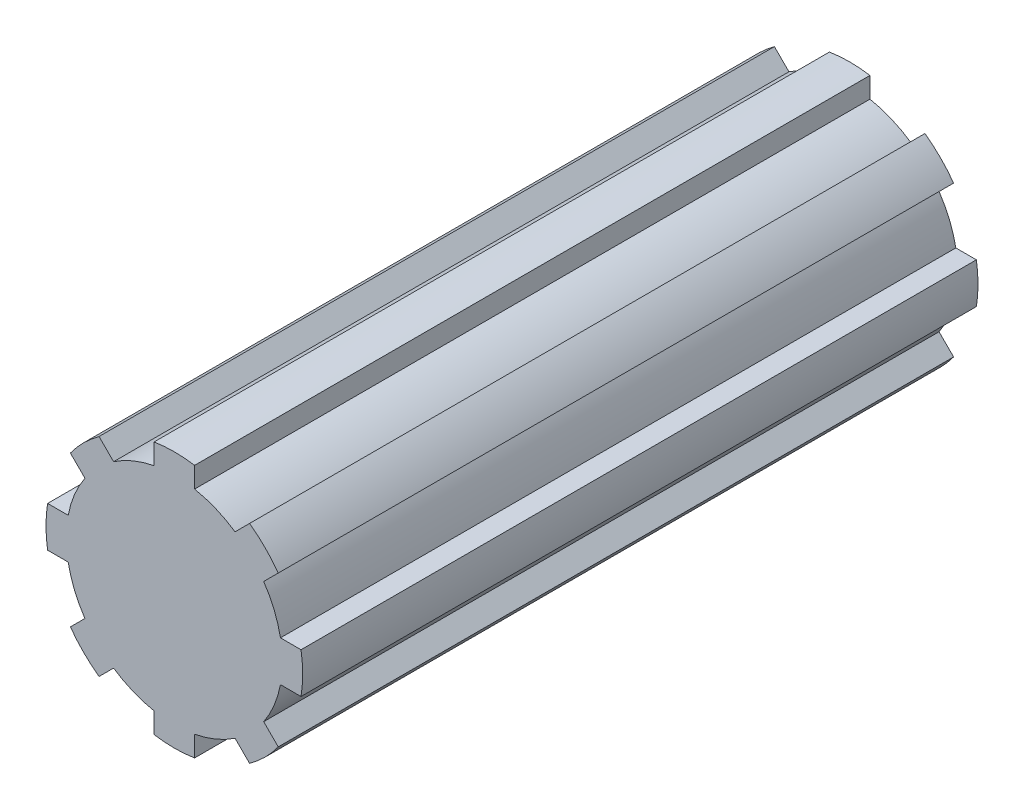
SolidWorks part; units mm, degrees
ref_plane "Front" through (0, 0, 0) normal (0, 0, 1) x (1, 0, 0)
ref_plane "Top" through (0, 0, 0) normal (0, 1, 0) x (1, 0, 0)
ref_plane "Right" through (0, 0, 0) normal (1, 0, 0) x (0, 0, -1)
sketch "Sketch1" plane through (0, 0, 0) normal (0, 0, 1) x (1, 0, 0)
  circle A0 centre (0, 0) radius 16
  dimension "d" = 32
extrude "BaseKey" add sketch "Sketch1" along normal mid plane 100
sketch "Sketch2" plane through (0, 0, 0) normal (0, 0, 1) x (1, 0, 0)
  line L0 (0, 9.5196) -> (0, -9.8317) construction
  line L1 (-3, 18.7617) -> (-3, 0)
  line L2 (-3, 0) -> (3, 0)
  line L3 (3, 0) -> (3, 18.7617)
  arc A0 (3, 18.7617) -> (-3, 18.7617) centre (0, 0) ccw
extrude "Rectangle" add sketch "Sketch2" along normal mid plane 100
pattern_circular "RectanglePat" count 8 over 360 about axis through (0, 0, 50) along (0, 0, -1) of "Rectangle"
equation "\"B1@Sketch2\" = \"B@Sketch2\" / 2"
equation "\"L1@Rectangle\" = \"L@BaseKey\""
